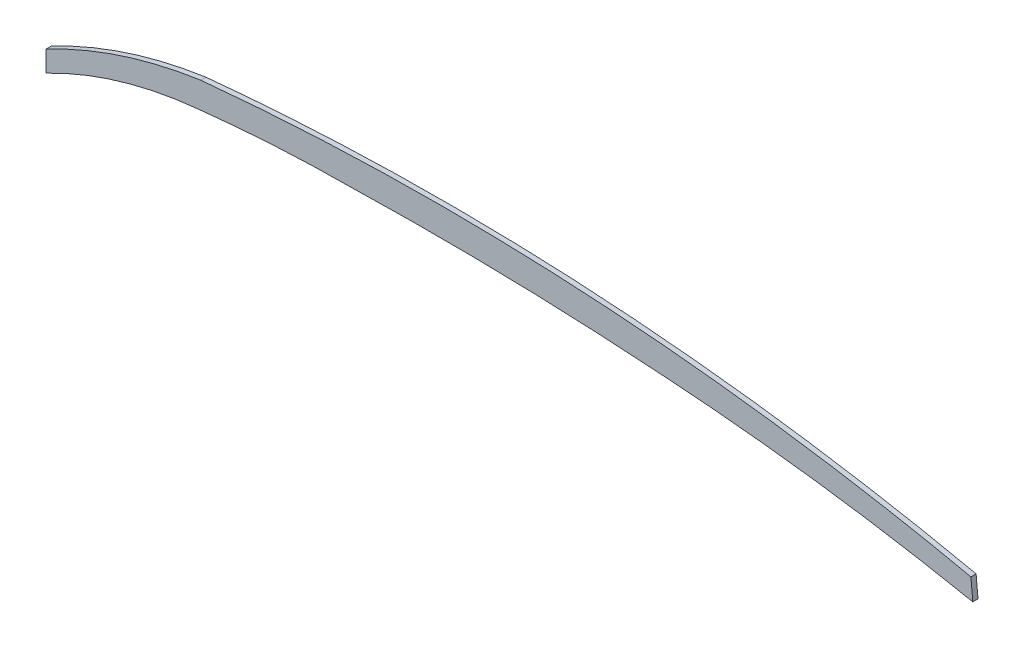
SolidWorks part; units mm, degrees
material "Balsa"
ref_plane "Front Plane" through (0, 0, 0) normal (0, 0, 1) x (1, 0, 0)
ref_plane "Top Plane" through (0, 0, 0) normal (0, 1, 0) x (1, 0, 0)
ref_plane "Right Plane" through (0, 0, 0) normal (1, 0, 0) x (0, 0, -1)
sketch "Sketch1" plane through (0, 0, 0) normal (0, 0, 1) x (1, 0, 0)
  line L0 (0, 85.9422) -> (0, 98.65)
  line L1 (566.0852, 89.3162) -> (564.9321, 101.9672)
  arc A6 (0, 85.9422) -> (92.3925, 113.3643) centre (117.1549, -139.4258) cw
  arc A7 (92.3925, 113.3643) -> (185.8959, 118.7314) centre (190.0181, -770.2591) cw
  arc A8 (0, 98.65) -> (94.4926, 129.4758) centre (136.5172, -159.5853) cw
  arc A9 (185.8959, 118.7314) -> (373.1011, 114.68) centre (236.8429, -1854.3329) cw
  arc A10 (373.1011, 114.68) -> (566.0852, 89.3162) centre (283.2319, -1315.9601) cw
  spline S6 degree 3 poles (1436.7994, -387.7706) (1129.2586, -95.659) (799.7428, 74.4986) (438.4396, 123.9344) (428.6248, 125.18) (408.999, 127.4765) (399.1847, 128.5281) (369.7378, 131.3942) (350.1011, 132.9202) (291.1746, 136.3528) (251.8686, 137.1157) (-132.8949, 129.6728) (-480.0018, 5.4463) (-829.0317, -254.0571) knots -1.993323 -1.993323 -1.993323 -1.993323 0.25 0.25 0.3125 0.3125 0.375 0.375 0.5 0.5 0.75 0.75 2.945884 2.945884 2.945884 2.945884 only from (564.9321, 101.9672) to (94.4926, 129.4758)
  spline S7 degree 3 poles (564.9321, 101.9672) (526.3055, 110.3588) (487.4057, 117.2346) (438.4396, 123.9344) (428.6248, 125.18) (408.999, 127.4765) (399.1847, 128.5281) (369.7378, 131.3942) (350.1011, 132.9202) (291.1746, 136.3528) (251.8686, 137.1157) (173.2133, 135.5942) (133.864, 133.3099) (94.4926, 129.4758) knots 0 0 0 0 0.25 0.25 0.3125 0.3125 0.375 0.375 0.5 0.5 0.75 0.75 1 1 1 1
  dimension "D4" = 92.3925
  dimension "D2" = 254
  dimension "D8" = 187.2051
  dimension "D9" = 28.7378
  dimension "D1" = 292.1
  dimension "D3" = 889
  dimension "D10" = 1973.7219
  dimension "D11" = 1433.46
  dimension "D5" = 27.4221
  dimension "D6" = 93.5034
  dimension "D7" = 32.7892
extrude "Boss-Extrude1" add sketch "Sketch1" against normal mid plane 3.175 contours L1 S7 A8 L0 A6 A7 A9 A10 region at (279.3924, 119.3664, 0)
equation "\"slotwidth\"=0.167708"
